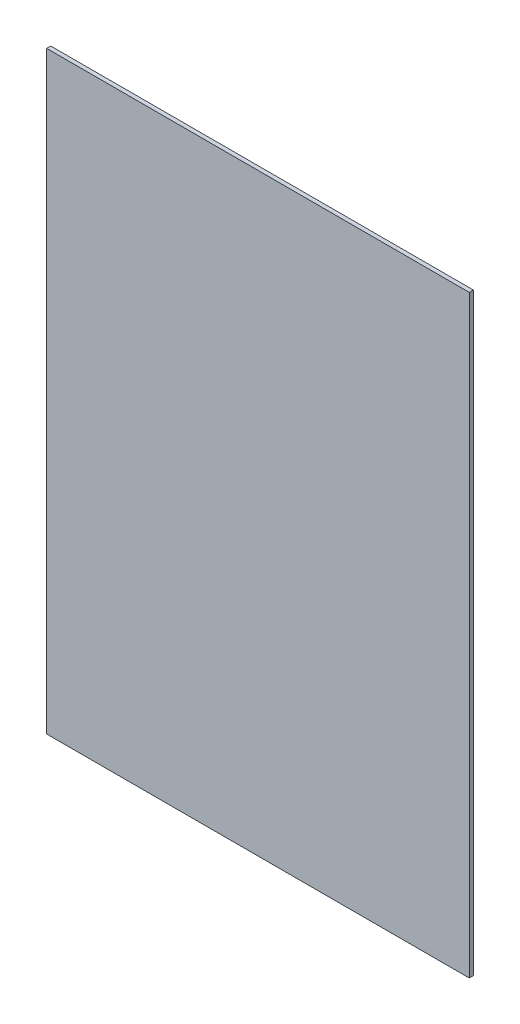
SolidWorks part; units mm, degrees
ref_plane "Спереди" through (0, 0, 0) normal (0, 0, 1) x (1, 0, 0)
ref_plane "Сверху" through (0, 0, 0) normal (0, 1, 0) x (1, 0, 0)
ref_plane "Справа" through (0, 0, 0) normal (1, 0, 0) x (0, 0, -1)
other "Configuration Table"
sketch "Эскиз2" plane through (0, 0, 0) normal (0, 0, 1) x (1, 0, 0)
  line L0 (518, 435.8) -> (518, -435.8) construction
  line L1 (1138.3, -435.8) -> (518, -435.8)
  line L2 (1138.3, -435.8) -> (1138.3, 435.8)
  line L3 (1138.3, 435.8) -> (518, 435.8)
  line L11 (518, -435.8) -> (518, 435.8)
  line L16 (1138.3, 435.8) -> (524, 435.8) construction
extrude "Бобышка-Вытянуть1" add sketch "Эскиз2" against normal blind 6
equation "\"Ширина груза\"= 420"
equation "\"Глубина груза\"= 490"
equation "\"Высота груза\"= 297"
equation "\"Ширина ячейки\"= \"Ширина груза\" + 10"
equation "\"Глубина ячейки\"= \"Глубина груза\" + 10"
equation "\"Высота ячейки\"= \"Высота груза\" + 10 + 13"
equation "\"Колво ячеек ширина\"= 2"
equation "\"Колво ячеек высота\"= 2"
equation "\"Толщина стенки\" = 6"
equation "\"Крепление дверцы\"= 5 "
equation "\"Ширина рейки\"= \"Толщина шестерни\""
equation "\"Высота рейки\"= 20"
equation "\"Высота пола\"= \"Толщина стенки\" * 2"
equation "\"Колво полозьев\"= 5"
equation "\"Отступ рейки\"= 20"
equation "\"Глубина каретки\"= \"Глубина ячейки\" + 30 + \"Мотор Y высота корпуса\" + 20"
equation "\"Длинна рейки\"= ( \"Ширина ячейки\" + \"Толщина стенки\" + \"Крепление дверцы\" ) * \"Колво ячеек ширина\" + \"Ширина ячейки выгрузки\" * \"Колво выгрузки\" + \"Толщина стенки\""
equation "\"Отступ шпильки\"= 26"
equation "\"Диаметр шпильки\"= 5"
equation "\"Длинна шпильки\"= ( \"Высота ячейки\" + \"Толщина стенки\" + \"Высота пола\" ) * \"Колво ячеек высота\" + ( \"Толщина стенки\" + \"Отступ рейки\" ) * 2 "
equation "\"Ширина пластины\"= 50  "
equation "\"Высота зона выгрузки\"= \"Высота ячейки\" * 2 + \"Толщина стенки\" * 2"
equation "\"Колво выгрузки\"= 1"
equation "\"Ширина ячейки выгрузки\"= \"Ширина ячейки\" + \"Толщина стенки\" + \"Отступ крепления мотора фиксации\"*2"
equation "\"Отступ крепления мотора фиксации\" = 30"
equation "\"Мотор X ширина корпуса\"= 42.3"
equation "\"Мотор X высота корпуса\"= 42.3"
equation "\"Мотор X длина корпуса\"= 40"
equation "\"Мотор X вылет вала\"= 19.8"
equation "\"Мотор Y ширина корпуса\"= 42.3"
equation "\"Мотор Y высота корпуса\"= 42.3"
equation "\"Мотор Y длина корпуса\"= 48"
equation "\"Мотор Y вылет вала\"= 30"
equation "\"Мотор Z ширина корпуса\"= 42"
equation "\"Мотор Z высота корпуса\"= 42"
equation "\"Мотор Z длина корпуса\"= 40"
equation "\"Мотор Z вылет вала\"= 23"
equation "\"Мотор диаметр вала ПРЕДВ\"= 5"
equation "\"Мотор шаг крепления ПРЕДВ\"= 31"
equation "\"Мотор диаметр отверстий ПРЕДВ\"= 3"
equation "\"Мотор глубина отверстий ПРЕДВ\"= 4.5"
equation "\"Мотор диаметр буртика ПРЕДВ\"= 22"
equation "\"Мотор высота буртика ПРЕДВ\"= 2"
equation "\"Мотор диаметр шкива ПРЕДВ\"= 16"
equation "\"Мотор длина шкива ПРЕДВ\"= 12"
equation "\"Мотор отступ шкива ПРЕДВ\"= 5"
equation "\"Мотор X шаг градусов\"= 1.8"
equation "\"Мотор Y шаг градусов\"= 1.8"
equation "\"Мотор Z шаг градусов\"= 1.8"
equation "\"Мотор Y диаметр ротора\"= 25.78"
equation "\"Толщина шестерни\"= 10"
equation "\"D1@Бобышка-Вытянуть1\"=\"Толщина стенки\""
